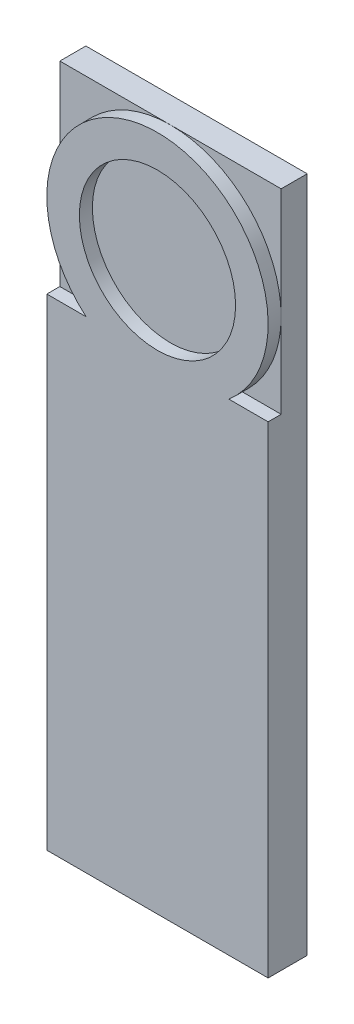
SolidWorks part; units mm, degrees
ref_plane "Front Plane" through (0, 0, 0) normal (0, 0, 1) x (1, 0, 0)
ref_plane "Top Plane" through (0, 0, 0) normal (0, 1, 0) x (1, 0, 0)
ref_plane "Right Plane" through (0, 0, 0) normal (1, 0, 0) x (0, 0, -1)
sketch "Sketch1" plane through (0, 0, 0) normal (0, 0, 1) x (1, 0, 0)
  circle A0 centre (0, 0) radius 12
  circle A1 centre (0, 0) radius 17
  dimension "D1" = 24
  dimension "D2" = 5
extrude "Boss-Extrude1" add sketch "Sketch1" along normal blind 4
sketch "Sketch2" plane through (0, 0, 0) normal (0, 0, -1) x (-1, 0, 0)
  line L1 (-17, 17) -> (17, 17)
  line L2 (-17, 17) -> (-17, -17)
  line L3 (-17, -17) -> (17, -17)
  line L4 (17, 17) -> (17, -17)
  line L5 (-17, 17) -> (17, -17) construction
  line L6 (-17, -17) -> (17, 17) construction
  circle A0 centre (0, 0) radius 17 construction
  circle A1 centre (0, 0) radius 17
  circle M1 centre (0, 0) radius 17
  circle M2 centre (0, 0) radius 12
extrude "Boss-Extrude3" add sketch "Sketch2" along normal blind 4 contours L1 L2 M1 | L2 L3 M1 | L4 L3 M1 | L4 L1 M1 | M1 M2 | M2 region at (13.2027, 13.2027, 0) region at (-13.2027, 13.2027, 0) region at (-11.6808, 11.6808, 0) region at (13.2027, -13.2027, 0) region at (-13.2027, -13.2027, 0) region at (0, 0, 0)
sketch "Sketch4" plane through (0, -17, 0) normal (0, -1, 0) x (1, 0, 0)
  line L0 (17, 4) -> (-17, 4) construction
  line L1 (-17, -4) -> (17, -4)
  line L2 (-17, -4) -> (-17, 4)
  line L3 (-17, 4) -> (17, 4)
  line L4 (17, -4) -> (17, 4)
  line L5 (17, 4) -> (-17, 4)
  point P7 (17, 4.4216)
  line M1 (17, 0) -> (0, 0)
  line M2 (0, 0) -> (-17, 0)
extrude "Boss-Extrude6" add sketch "Sketch4" against normal blind 4 contours L4 L3 L2 M1 M2 region at (0, -17, 2)
sketch "Sketch5" plane through (0, -17, 0) normal (0, -1, 0) x (1, 0, 0)
  line L0 (17, -4) -> (17, 4) construction
  line L1 (17, -4) -> (-17, -4) construction
  line L2 (-17, 4) -> (17, 4) construction
  line L3 (-17, -4) -> (-17, 4) construction
  line L4 (17, -4) -> (17, 4)
  line L5 (17, -4) -> (-17, -4)
  line L6 (-17, 4) -> (17, 4)
  line L7 (-17, -4) -> (-17, 4)
extrude "Boss-Extrude7" add sketch "Sketch5" along normal blind 70
sketch "Sketch6" plane through (0, 0, 4) normal (0, 0, 1) x (1, 0, 0)
  line L0 (-10.9545, -13) -> (-17, -13) construction
  line L1 (-17, -13) -> (-17, -87) construction
  line L2 (17, -87) -> (-17, -87) construction
  line L3 (17, -13) -> (17, -87) construction
  line L4 (10.9545, -13) -> (17, -13) construction
  line L5 (-10.9545, -13) -> (-17, -13)
  line L6 (-17, -13) -> (-17, -87)
  line L7 (17, -87) -> (-17, -87)
  line L8 (17, -13) -> (17, -87)
  line L9 (10.9545, -13) -> (17, -13)
  circle A0 centre (0, 0) radius 12 construction
  arc A1 (10.9545, -13) -> (-10.9545, -13) centre (0, 0) ccw construction
  circle A2 centre (0, 0) radius 12
  arc A3 (10.9545, -13) -> (-10.9545, -13) centre (0, 0) ccw
extrude "Cut-Extrude1" cut sketch "Sketch6" against normal blind 2
